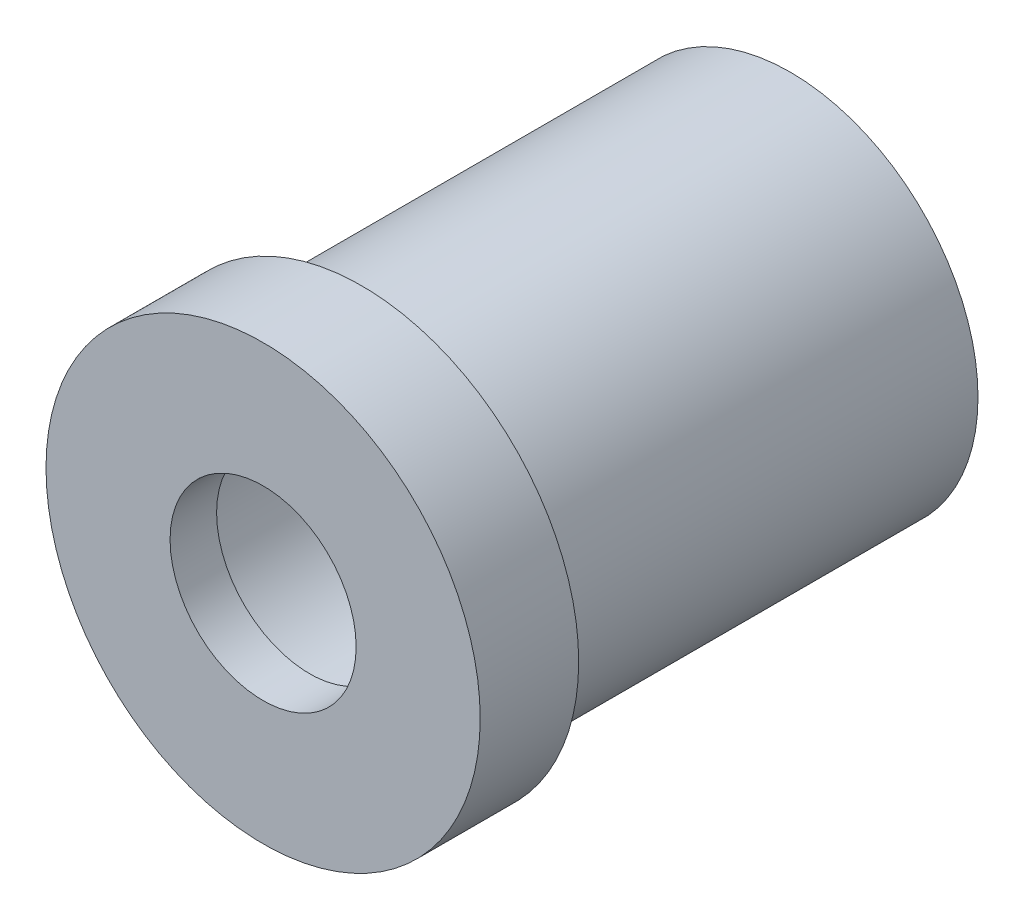
SolidWorks part; units mm, degrees
ref_plane "Front Plane" through (0, 0, 0) normal (0, 0, 1) x (1, 0, 0)
ref_plane "Top Plane" through (0, 0, 0) normal (0, 1, 0) x (1, 0, 0)
ref_plane "Right Plane" through (0, 0, 0) normal (1, 0, 0) x (0, 0, -1)
sketch "Sketch1" plane through (0, 0, 0) normal (0, 0, 1) x (1, 0, 0)
  circle A0 centre (0, 0) radius 12.1
  dimension "D1" = 24.2
extrude "Boss-Extrude1" add sketch "Sketch1" along normal mid plane 34
sketch "Sketch2" plane through (0, 0, 17) normal (0, 0, 1) x (1, 0, 0)
  circle A0 centre (0, 0) radius 7.7
  dimension "D1" = 15.4
extrude "Cut-Extrude1" cut sketch "Sketch2" against normal through all
sketch "Sketch3" plane through (0, 0, 17) normal (0, 0, 1) x (1, 0, 0)
  circle A0 centre (0, 0) radius 14
  circle M3 centre (0, 0) radius 12.1
  dimension "D1" = 28
extrude "Boss-Extrude2" add sketch "Sketch3" against normal blind 6.35 contours A0 M3 region at (-13.604, 0, 17)
sketch "Sketch4" plane through (0, 0, 17) normal (0, 0, 1) x (1, 0, 0)
  circle A0 centre (0, 0) radius 6
  circle M2 centre (0, 0) radius 7.7
  dimension "D1" = 12
extrude "Boss-Extrude3" add sketch "Sketch4" against normal blind 3 contours A0 M2 region at (-7.4822, 0, 17)
